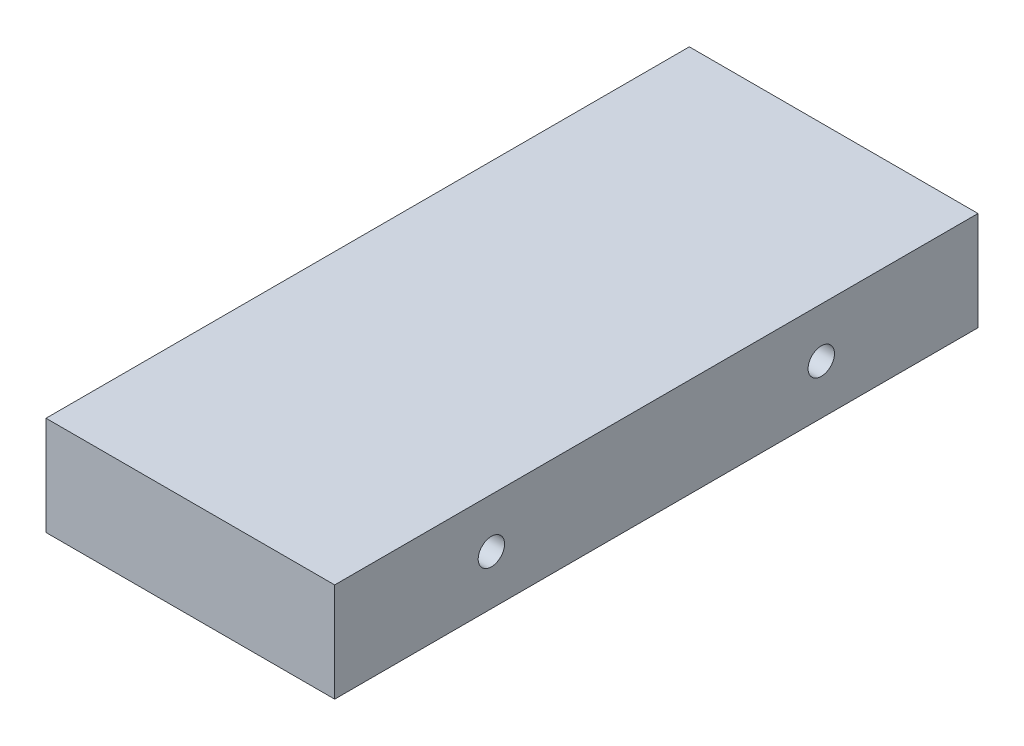
SolidWorks part; units mm, degrees
ref_plane "Front Plane" through (0, 0, 0) normal (0, 0, 1) x (1, 0, 0)
ref_plane "Top Plane" through (0, 0, 0) normal (0, 1, 0) x (1, 0, 0)
ref_plane "Right Plane" through (0, 0, 0) normal (1, 0, 0) x (0, 0, -1)
sketch "Sketch1" plane through (0, 0, 0) normal (1, 0, 0) x (0, 0, -1)
  line L1 (-39, 6) -> (39, 6)
  line L2 (-39, 6) -> (-39, -6)
  line L3 (-39, -6) -> (39, -6)
  line L4 (39, 6) -> (39, -6)
  line L5 (-39, 6) -> (39, -6) construction
  line L6 (-39, -6) -> (39, 6) construction
  circle A0 centre (-20, 0) radius 4
  circle A1 centre (-20, 0) radius 1.6
  circle A2 centre (20, 0) radius 4
  circle A3 centre (20, 0) radius 1.6
  circle A4 centre (-34, 0) radius 1.621
  circle A5 centre (34, 0) radius 1.621
  point P0 (0, 0)
  point P16 (0, 0)
  point P17 (0, 0)
  dimension "D5" = 3.2
  dimension "D6" = 8
  dimension "D7" = 3.242
  dimension "D8" = 68
  dimension "D9" = 34
  dimension "D1" = 12
  dimension "D2" = 78
  dimension "D3" = 20
  dimension "D4" = 20
extrude "Boss-Extrude1" add sketch "Sketch1" along normal blind 35 contours L2 L3 L4 L1
extrude "Cut-Extrude1" cut sketch "Sketch1<4>" along normal blind 27 contours A0 | A2
sketch "Sketch1<4>" plane through (0, 0, 0) normal (1, 0, 0) x (0, 0, -1) same geometry as "Sketch1"
extrude "Cut-Extrude2" cut sketch "Sketch1<5>" along normal blind 35 contours A3 | A1
sketch "Sketch1<5>" plane through (0, 0, 0) normal (1, 0, 0) x (0, 0, -1) same geometry as "Sketch1"
extrude "Cut-Extrude3" cut sketch "Sketch1<6>" along normal blind 12 contours A5 | A4
sketch "Sketch1<6>" plane through (0, 0, 0) normal (1, 0, 0) x (0, 0, -1) same geometry as "Sketch1"
